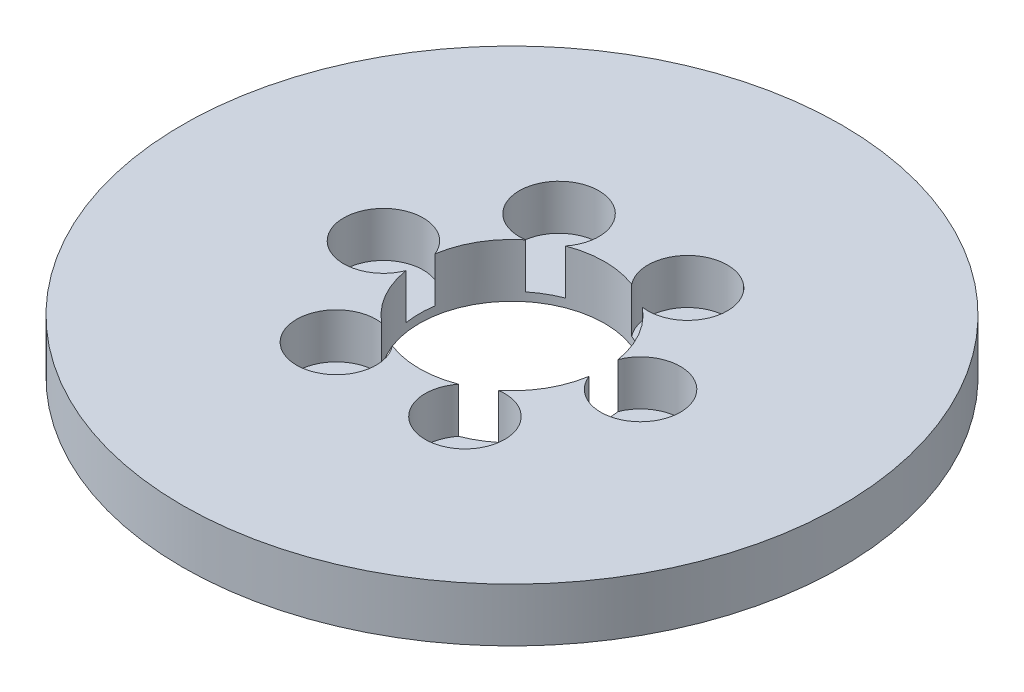
SolidWorks part; units mm, degrees
ref_plane "Front Plane" through (0, 0, 0) normal (0, 0, 1) x (1, 0, 0)
ref_plane "Top Plane" through (0, 0, 0) normal (0, 1, 0) x (1, 0, 0)
ref_plane "Right Plane" through (0, 0, 0) normal (1, 0, 0) x (0, 0, -1)
sketch "Sketch1" plane through (0, 0, 0) normal (0, 1, 0) x (1, 0, 0)
  circle A0 centre (0, 0) radius 80
  dimension "FLANGE_OD" = 160
extrude "Boss-Extrude1" add sketch "Sketch1" along normal blind 13
sketch "Sketch2" plane through (0, 0, 0) normal (0, 1, 0) x (1, 0, 0)
  circle A0 centre (0, 0) radius 22.5
  dimension "BORE_D" = 45
extrude "Cut-Extrude1" cut sketch "Sketch2" along normal through all
sketch "Sketch3" plane through (0, 13, 0) normal (0, 1, 0) x (1, 0, 0)
  circle A0 centre (0, 0) radius 31.2101 construction
  circle A1 centre (-31.2101, 0) radius 9.658
  dimension "BOLT_D" = 19.3161
  dimension "BOLT_PCD" = 62.4202
extrude "Cut-Extrude2" cut sketch "Sketch3" against normal blind 10.9498
pattern_circular "CirPattern1" count 6 over 360 about axis through (0, 0, 0) along (0, 1, 0) of "Cut-Extrude2"
